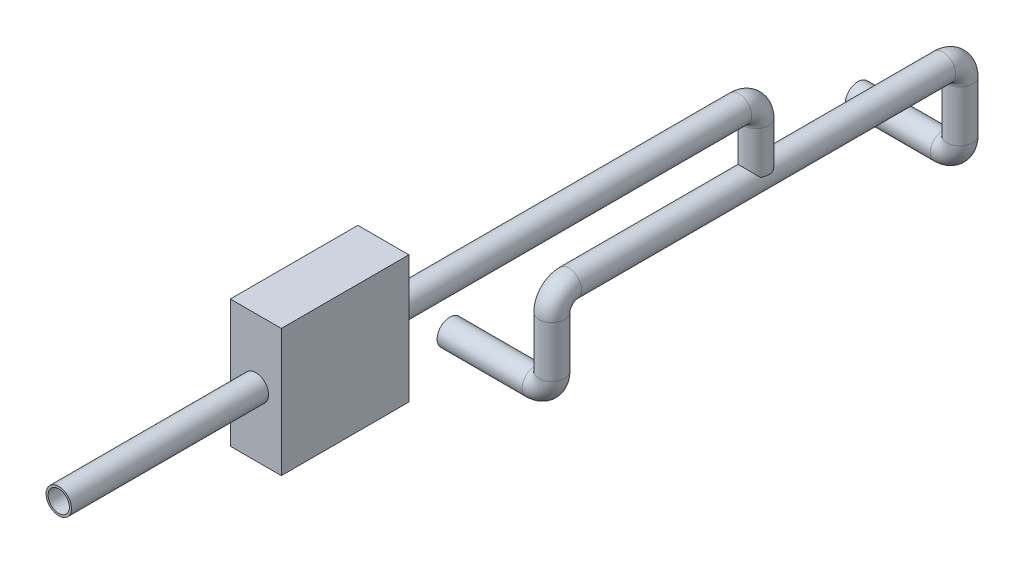
SolidWorks part; units mm, degrees
material "ABS PC"
ref_plane "Front Plane" through (0, 0, 0) normal (0, 0, 1) x (1, 0, 0)
ref_plane "Top Plane" through (0, 0, 0) normal (0, 1, 0) x (1, 0, 0)
ref_plane "Right Plane" through (0, 0, 0) normal (1, 0, 0) x (0, 0, -1)
sketch3d "3DSketch1"
  line L0 (0, 0, 0) -> (0, 0, 110)
  line L1 (0, -10, 120) -> (0, -40, 120)
  line L2 (-10, -50, 120) -> (-60, -50, 120)
  line L3 (0, 0, 0) -> (0, 0, -110)
  line L4 (0, -10, -120) -> (0, -40, -120)
  line L5 (-10, -50, -120) -> (-60, -50, -120)
  arc A0 (0, -40, -120) -> (-10, -50, -120) centre (-10, -40, -120) ccw
  arc A1 (0, -10, -120) -> (0, 0, -110) centre (0, -10, -110) ccw
  arc A2 (0, -10, 120) -> (0, 0, 110) centre (0, -10, 110) ccw
  arc A3 (-10, -50, 120) -> (0, -40, 120) centre (-10, -40, 120) ccw
  point P10 (0, -50, -120)
  point P11 (-10, -40, -130)
  point P14 (0, 0, -120)
  point P15 (10, -10, -110)
  point P18 (0, 0, 120)
  point P19 (-10, -10, 110)
  point P22 (0, -50, 120)
  point P23 (-10, -40, 130)
  dimension "D4" = 10
  dimension "D1" = 60
  dimension "D2" = 50
  dimension "D3" = 240
sweep "Sweep1" add path "3DSketch1" circular profile diameter 15 parameters "D3"=15
sketch "Sketch30" plane through (0, 0, 0) normal (1, 0, 0) x (0, 0, -1)
  line L0 (0, 3.789) -> (0, 28.789)
  line L1 (-10, 38.789) -> (-410, 38.789)
  arc A0 (0, 28.789) -> (-10, 38.789) centre (-10, 28.789) ccw
  point P7 (0, 38.789)
  point P8 (0, 38.789)
  dimension "D3" = 400
  dimension "D2" = 10
  dimension "D1" = 35
sweep "Sweep2" add path "Sketch30" circular profile diameter 15 parameters "D3"=15
sweep "Cut-Sweep1" cut path "3DSketch1<2>" circular profile diameter 12.5 parameters "D3"=12.5
sketch3d "3DSketch1<2>" same geometry as "3DSketch1"
sweep "Cut-Sweep2" cut path "Sketch30<2>" circular profile diameter 12.5 parameters "D3"=12.5
sketch "Sketch30<2>" plane through (0, 0, 0) normal (1, 0, 0) x (0, 0, -1) same geometry as "Sketch30"
sketch "Sketch35" plane through (0, 0, 0) normal (1, 0, 0) x (0, 0, -1)
  line L0 (-10, 46.289) -> (-410, 46.289) construction
  line L1 (-294.1055, 1.289) -> (-219.1055, 1.289)
  line L2 (-294.1055, 1.289) -> (-294.1055, 76.289)
  line L3 (-294.1055, 76.289) -> (-219.1055, 76.289)
  line L4 (-219.1055, 1.289) -> (-219.1055, 76.289)
  line L5 (-294.1055, 1.289) -> (-219.1055, 76.289) construction
  line L6 (-294.1055, 76.289) -> (-219.1055, 1.289) construction
  point P0 (-256.6055, 38.789)
  dimension "D1" = 75
  dimension "D2" = 7.5
  dimension "D3" = 75
extrude "Boss-Extrude1" add sketch "Sketch35" along normal mid plane 30
sketch "Sketch48" plane through (-15, 0, 0) normal (-1, 0, 0) x (0, 0, 1)
  line L0 (219.1055, 46.289) -> (294.1055, 46.289) construction
  line L1 (219.1055, 76.289) -> (294.1055, 76.289) construction
  line L2 (219.1055, 1.289) -> (219.1055, 76.289) construction
  line L3 (294.1055, 76.289) -> (294.1055, 1.289) construction
  line L4 (219.1055, 21.289) -> (294.1055, 21.289) construction
  line L5 (294.1055, 1.289) -> (219.1055, 1.289) construction
  text T0 "BUBBLE TRAP" font "Century Gothic" height in points 28
  text T1 "HEAT EXCHANGER" font "Century Gothic" height in points 22
  dimension "D1" = 30
  dimension "D2" = 20
extrude "Boss-Extrude2" add sketch "Sketch48" along normal blind 1
